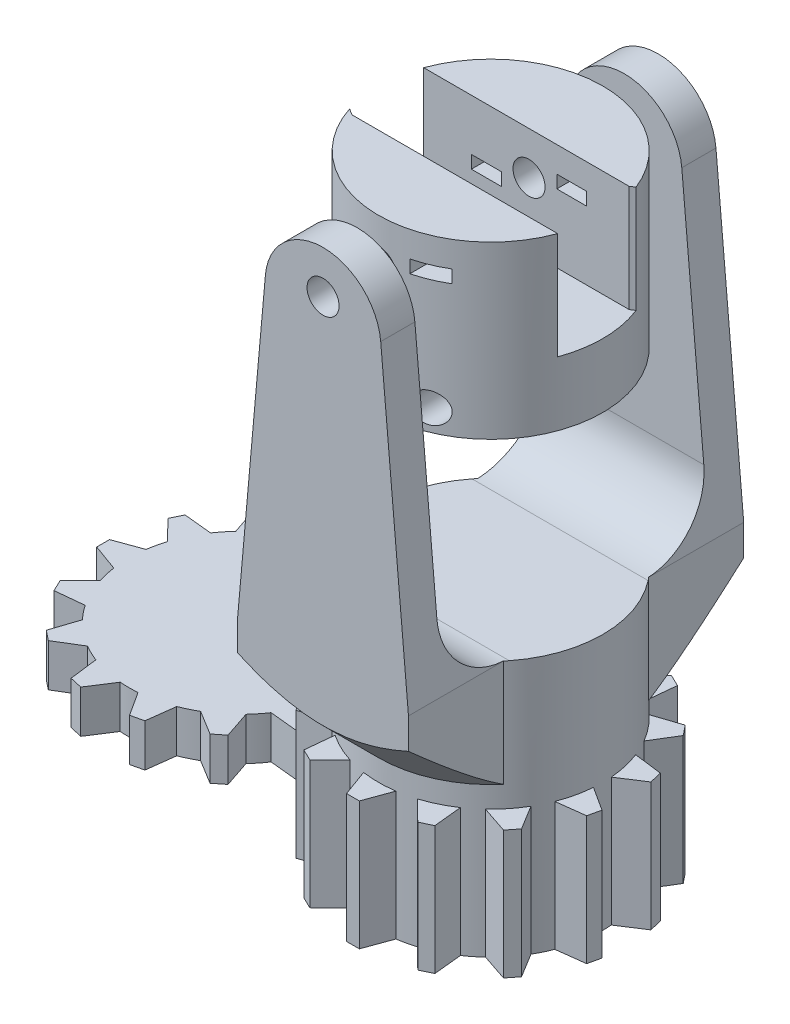
SolidWorks part; units mm, degrees
ref_plane "Front Plane" through (0, 0, 0) normal (0, 0, 1) x (1, 0, 0)
ref_plane "Top Plane" through (0, 0, 0) normal (0, 1, 0) x (1, 0, 0)
ref_plane "Right Plane" through (0, 0, 0) normal (1, 0, 0) x (0, 0, -1)
sketch "Sketch1" plane through (0, 0, 0) normal (0, 1, 0) x (1, 0, 0)
  circle A0 centre (0, 0) radius 26.25
  dimension "D1" = 52.5
extrude "Boss-Extrude1" add sketch "Sketch1" along normal blind 145
sketch "Sketch2" plane through (0, 145, 0) normal (0, 1, 0) x (1, 0, 0)
  line L5 (-24.6664, 8.9794) -> (23.4506, 8.9794)
  line L7 (-23.4506, -8.9794) -> (24.6664, -8.9794)
  line L9 (-24.6664, 8.9794) -> (24.6664, -8.9794) construction
  line L10 (-23.4506, -8.9794) -> (23.4506, 8.9794) construction
  circle A1 centre (0, 0) radius 26.25 construction
  arc A2 (-24.6664, 8.9794) -> (-23.4506, -8.9794) centre (-18.6625, 0.3653) ccw
  arc A3 (23.4506, 8.9794) -> (24.6664, -8.9794) centre (29.4545, 0.3653) cw
  point P0 (0, 0)
  dimension "D2" = 10.5
  dimension "D3" = 10.5
  dimension "D1" = 18
  dimension "D4" = 48.117
extrude "Cut-Extrude1" cut sketch "Sketch2" against normal blind 25
sketch "Sketch3" plane through (0, 0, 0) normal (0, 0, 1) x (1, 0, 0)
  line L0 (-10, 110) -> (10, 110) construction
  line L1 (26.25, 120) -> (24.4361, 120) construction
  circle A0 centre (-10, 110) radius 3.5
  circle A1 centre (10, 110) radius 3.5
  point P4 (0, 110)
  dimension "D1" = 7
  dimension "D2" = 7
  dimension "D3" = 10
  dimension "D4" = 20
extrude "Cut-Extrude2" cut sketch "Sketch3" against normal through all both and the other way through all
sketch "Sketch4" plane through (0, 0, 0) normal (0, -1, 0) x (1, 0, 0)
  circle A0 centre (0, 0) radius 3.95
  dimension "D1" = 7.9
extrude "Boss-Extrude2" add sketch "Sketch4" along normal blind 7
sketch "Sketch5" plane through (0, 0, 0) normal (0, -1, 0) x (1, 0, 0)
  circle A0 centre (0, 0) radius 5
  dimension "D1" = 10
extrude "Boss-Extrude3" add sketch "Sketch5" along normal blind 1
sketch "Sketch6" plane through (0, 0, 0) normal (0, 0, 1) x (1, 0, 0)
  line L1 (26.25, 120) -> (24.4361, 120) construction
  line L2 (6.5, 136) -> (13.5, 136)
  line L3 (-13.5, 133) -> (-6.5, 133)
  line L4 (-13.5, 133) -> (-13.5, 130)
  line L5 (-13.5, 130) -> (-6.5, 130)
  line L6 (-6.5, 133) -> (-6.5, 130)
  line L7 (6.5, 136) -> (6.5, 139)
  line L8 (6.5, 139) -> (13.5, 139)
  line L9 (13.5, 136) -> (13.5, 139)
  line L10 (-24.6664, 120) -> (-26.25, 120) construction
  dimension "D1" = 7
  dimension "D2" = 7
  dimension "D3" = 3
  dimension "D4" = 3
  dimension "D5" = 16
  dimension "D6" = 10
  dimension "D7" = 13
  dimension "D8" = 13.5
extrude "Cut-Extrude3" cut sketch "Sketch6" against normal through all both and the other way through all
sketch "Sketch8" plane through (0, 0, 0) normal (0, 0, 1) x (1, 0, 0)
  line L0 (-26.25, 120) -> (-26.25, 0) construction
  line L1 (-26.25, 105) -> (26.25, 105)
  line L2 (-26.25, 105) -> (-26.25, 60)
  line L3 (-26.25, 60) -> (26.25, 60)
  line L4 (26.25, 105) -> (26.25, 60)
  line L5 (26.25, 0) -> (26.25, 120) construction
  line L6 (24.6664, 145) -> (-24.9989, 145) construction
  line L7 (-26.25, 0) -> (26.25, 0) construction
  dimension "D1" = 40
  dimension "D2" = 60
extrude "Cut-Extrude5" cut sketch "Sketch8" against normal through all both and the other way through all
sketch "Sketch9" plane through (0, 0, 0) normal (1, 0, 0) x (0, 0, -1)
  line L7 (26.25, 145) -> (8.9794, 145) construction
  line L8 (31.25, 145) -> (39.25, 145)
  line L9 (31.25, 145) -> (31.25, 55)
  line L10 (31.25, 55) -> (39.25, 55)
  line L11 (39.25, 145) -> (39.25, 55)
  line L12 (26.25, 0) -> (26.25, 60) construction
  dimension "D3" = 5
  dimension "D1" = 8
  dimension "D2" = 90
extrude "Boss-Extrude4" add sketch "Sketch9" along normal mid plane 40 separate body
sketch "Sketch10" plane through (0, 0, -31.25) normal (0, 0, 1) x (1, 0, 0)
  line L0 (26.25, 60) -> (-26.25, 60) construction
  line L1 (-20, 60) -> (20, 60)
  line L2 (-20, 60) -> (-20, 55)
  line L3 (-20, 55) -> (20, 55)
  line L4 (20, 60) -> (20, 55)
  line L5 (-20, 145) -> (-20, 55) construction
  line L6 (20, 145) -> (20, 55) construction
  line L7 (20, 55) -> (-20, 55) construction
extrude "Boss-Extrude5" add sketch "Sketch10" along normal up to surface (14.2482 mm away) up to face at (0, 0, 26.25)
sketch "Sketch11" plane through (0, 0, -39.25) normal (0, 0, -1) x (-1, 0, 0)
  line L0 (-20, 60) -> (-13.5, 132.6539)
  line L1 (-20, 55) -> (20, 55) construction
  line L2 (13.5, 132.6539) -> (20, 60)
  line L3 (-20, 145) -> (20, 145) construction
  line L4 (-20, 60) -> (-20, 145)
  line L5 (-20, 145) -> (20, 145)
  line L6 (20, 145) -> (20, 60)
  line L7 (-20, 60) -> (20, 60) construction
  line L8 (-20, 60) -> (20, 60) construction
  arc A0 (-13.5, 132.6539) -> (13.5, 132.6539) centre (0, 131.4461) cw
  point P15 (0, 55)
  point P20 (-20, 49.2254)
  line M3 (20, 55) -> (20, 145)
  line M4 (20, 145) -> (-20, 145)
  line M5 (-20, 145) -> (-20, 55)
  dimension "D1" = 27
extrude "Cut-Extrude6" cut sketch "Sketch11" against normal up to surface (8 mm away) contours L0 A0 L5 M5 | A0 L2 M4 M3 region at (16.7856, 118.9686, -39.25) region at (-16.7856, 118.9686, -39.25) up to face at (0, 102.5, -31.25)
sketch "Sketch18" plane through (0, 0, 0) normal (1, 0, 0) x (0, 0, -1)
  line L0 (-8.0073, 145) -> (-26.25, 145) construction
  line L1 (-39.25, 145) -> (-31.25, 145)
  line L2 (-39.25, 145) -> (-39.25, 55)
  line L3 (-39.25, 55) -> (-31.25, 55)
  line L4 (-31.25, 145) -> (-31.25, 55)
  line L5 (-26.25, 145) -> (-26.25, 105) construction
  dimension "D1" = 90
  dimension "D2" = 8
  dimension "D3" = 5
extrude "Boss-Extrude7" add sketch "Sketch18" along normal mid plane 40 separate body contours L2 L3 L4 L1
sketch "Sketch19" plane through (0, 0, 31.25) normal (0, 0, -1) x (-1, 0, 0)
  line L0 (-20, 145) -> (-20, 55) construction
  line L1 (-20, 60) -> (20, 60)
  line L2 (-20, 60) -> (-20, 55)
  line L3 (-20, 55) -> (20, 55)
  line L4 (20, 60) -> (20, 55)
  line L5 (26.25, 60) -> (-26.25, 60) construction
extrude "Boss-Extrude8" add sketch "Sketch19" along normal up to surface (14.2482 mm away) up to face at (0, 0, 26.25)
sketch "Sketch20" plane through (0, 0, 39.25) normal (0, 0, 1) x (1, 0, 0)
  line L0 (-20, 60) -> (20, 60) construction
  line L1 (-20, 145) -> (-20, 55) construction
  line L2 (-20, 55) -> (-20, 60) construction
  line L4 (-20, 60) -> (-13.5, 132.6539)
  line L5 (-20, 60) -> (-20, 145)
  line L6 (13.5, 132.6539) -> (20, 60)
  line L7 (20, 145) -> (-20, 145) construction
  line L8 (-20, 145) -> (20, 145)
  line L9 (20, 145) -> (20, 60)
  arc A0 (-13.5, 132.6539) -> (13.5, 132.6539) centre (0, 131.4461) cw
  line M4 (-20, 145) -> (-20, 55)
  line M6 (20, 55) -> (20, 145)
  line M7 (20, 145) -> (-20, 145)
  dimension "D1" = 27
extrude "Cut-Extrude7" cut sketch "Sketch20" against normal up to surface (8 mm away) contours L4 A0 L8 M4 | A0 L6 M7 M6 region at (-16.7856, 118.9686, 39.25) region at (16.7856, 118.9686, 39.25) up to face at (0, 102.5, 31.25)
sketch "Sketch7" plane through (0, 0, 0) normal (0, 0, 1) x (1, 0, 0)
  line L0 (24.6664, 145) -> (-24.9989, 145) construction
  circle A0 centre (0, 135) radius 3.75
  dimension "D1" = 7.5
  dimension "D2" = 10
extrude "Cut-Extrude4" cut sketch "Sketch7" against normal through all both and the other way through all
fillet "Fillet3" radius 15 2 edges at (0, 60, -31.25) (0, 60, 31.25)
chamfer "Chamfer2" distance 20 angle 45 2 edges at (0, 55, -26.25) (0, 55, 26.25)
ref_plane "Plane3" through (0, 30, 0) normal (0, -1, 0) x (-1, 0, 0)
sketch "Sketch22" plane through (0, 30, 0) normal (0, -1, 0) x (-1, 0, 0)
  line L0 (0, 0) -> (0, 36.93) construction
  line L1 (-1.5, 32.25) -> (1.5, 32.25)
  line L2 (1.5, 32.25) -> (3.7836, 25.9759)
  line L3 (0, 32.25) -> (0, 26.25)
  line L4 (-1.5, 32.25) -> (-3.7836, 25.9759)
  line L5 (-3.7836, 25.9759) -> (3.7836, 25.9759)
  circle A0 centre (0, 0) radius 26.25 construction
  arc A1 (20, 17.0018) -> (-20, 17.0018) centre (0, 0) ccw construction
  dimension "D1" = 110
  dimension "D2" = 6
  dimension "D3" = 1.5
extrude "Boss-Extrude9" add sketch "Sketch22" along normal up to surface (30 mm away) contours L5 L0 L3 L1 L4 | L0 L5 L2 L1 L3 region at (-1.4031, 30, -28.661) region at (1.4031, 30, -28.661) up to face at (0, 0, 5)
pattern_circular "CirPattern1" count 14 over 360 about axis through (0, 0, 0) along (0, 1, 0) of "Boss-Extrude9"
ref_plane "Plane4" through (0, 15, 0) normal (0, 1, 0) x (1, 0, 0)
sketch "Sketch23" plane through (0, 15, 0) normal (0, 1, 0) x (1, 0, 0)
  circle A0 centre (-58.5, 0) radius 26.25
  point P2 (0, 0)
  point P4 (0, 0)
  dimension "D1" = 52.5
  dimension "D2" = 58.5
extrude "Boss-Extrude10" add sketch "Sketch23" along normal mid plane 10 separate body
sketch "Sketch24" plane through (0, 10, 0) normal (0, -1, 0) x (1, 0, 0)
  line L0 (-58.5, 0) -> (-21.887, 0) construction
  line L1 (-32.5241, 3.7836) -> (-26.25, 1.5)
  line L2 (-26.25, 1.5) -> (-26.25, -1.5)
  line L3 (-32.25, 0) -> (-26.25, 0)
  line L4 (-32.5241, -3.7836) -> (-26.25, -1.5)
  line L5 (-32.5241, 3.7836) -> (-32.5241, -3.7836)
  circle A0 centre (-58.5, 0) radius 26.25 construction
  circle M5 centre (-58.5, 0) radius 26.25
  dimension "D1" = 110
  dimension "D2" = 6
  dimension "D3" = 1.5
extrude "Boss-Extrude11" add sketch "Sketch24" against normal up to surface (10 mm away) contours L3 L2 L1 M5 | L4 L2 L3 M5 region at (-29.7268, 10, 1.4024) region at (-29.7268, 10, -1.4024) up to face at (-58.5, 20, 26.25)
pattern_circular "CirPattern2" count 14 over 360 about axis through (-58.5, 10, 0) along (0, 1, 0) of "Boss-Extrude11"
sketch "Sketch25" plane through (0, 10, 0) normal (0, -1, 0) x (1, 0, 0)
  circle A0 centre (-58.5, 0) radius 5
  dimension "D1" = 10
extrude "Boss-Extrude12" add sketch "Sketch25" along normal blind 5
sketch "Sketch26" plane through (0, 5, 0) normal (0, -1, 0) x (1, 0, 0)
  line L0 (-60.1, 2.0494) -> (-60.1, -2.0494)
  line L1 (-56.9, 2.0494) -> (-56.9, -2.0494)
  arc A0 (-60.1, -2.0494) -> (-56.9, -2.0494) centre (-58.5, 0) ccw
  arc A1 (-56.9, 2.0494) -> (-60.1, 2.0494) centre (-58.5, 0) ccw
  dimension "D1" = 5.2
  dimension "D2" = 3.2
  dimension "D3" = 1.6
extrude "Cut-Extrude8" cut sketch "Sketch26" against normal blind 6.1
fillet "Fillet4" radius 5 1 edges at (-58.5, 10, 5)
equation "\"Overall Diameter\"= 52.5"
equation "\"Front Slot Width\"= 18"
equation "\"Back Slot Width\"= 20.8"
equation "\"Slot Depth\"= 25"
equation "\"Bearing OD\"= 22.3"
equation "\"Bearing ID\"= 7.9"
equation "\"D1@Sketch1\"=\"Overall Diameter\""
equation "\"D1@Sketch2\"=\"Front Slot Width\""
equation "\"D3@Sketch2\"=10.5"
equation "\"D1@Cut-Extrude1\"=\"Slot Depth\""
equation "\"Bearing ID Depth\"= 7"
equation "\"Bearing ID Stopper\"= 10"
equation "\"Bearing ID Stopper Depth\"= 1"
equation "\"D1@Sketch4\"=\"Bearing ID\""
equation "\"D1@Boss-Extrude2\"=\"Bearing ID Depth\""
equation "\"D1@Sketch5\"=\"Bearing ID Stopper\""
equation "\"D1@Boss-Extrude3\"=\"Bearing ID Stopper Depth\""
equation "\"Pivot Arm Length\"= 90"
equation "\"Body Separation\"= 5"
equation "\"Arm Thickness\" = 8"
equation "\"D1@Sketch18\"=\"Pivot Arm Length\""
equation "\"D2@Sketch18\"=\"Arm Thickness\""
equation "\"D3@Sketch18\"=\"Body Separation\""
equation "\"Arm Width\"= 40"
equation "\"D1@Boss-Extrude7\"=\"Arm Width\""
equation "\"D2@Sketch9\"=\"Pivot Arm Length\""
equation "\"D3@Sketch9\"=\"Body Separation\""
equation "\"D1@Sketch9\"=\"Arm Thickness\""
equation "\"D1@Boss-Extrude4\"=\"Arm Width\""
equation "\"Gear Tooth Heigth\"= 6"
equation "\"Gear Tooth Width\"= 3"
equation "\"Geat Tooth Angle\"= 110"
equation "\"D3@Sketch22\"=\"Gear Tooth Width\"/2"
equation "\"D2@Sketch22\"=\"Gear Tooth Heigth\""
equation "\"D1@Sketch22\"=\"Geat Tooth Angle\""
equation "\"D1@Sketch23\"=\"Overall Diameter\""
equation "\"D2@Sketch23\"=\"Overall Diameter\"+\"Gear Tooth Heigth\""
equation "\"D1@Sketch24\"=\"Geat Tooth Angle\""
equation "\"D2@Sketch24\"=\"Gear Tooth Heigth\""
equation "\"D3@Sketch24\"=\"Gear Tooth Width\"/2"
equation "\"Stepper Attachment Diameter\"= 5.2"
equation "\"Stepper Attachment Width\"= 3.2"
equation "\"D1@Sketch26\"=\"Stepper Attachment Diameter\""
equation "\"D2@Sketch26\"=\"Stepper Attachment Width\""
equation "\"D3@Sketch26\"=\"Stepper Attachment Width\"/2"
equation "\"Number of Teeth\"= 14"
